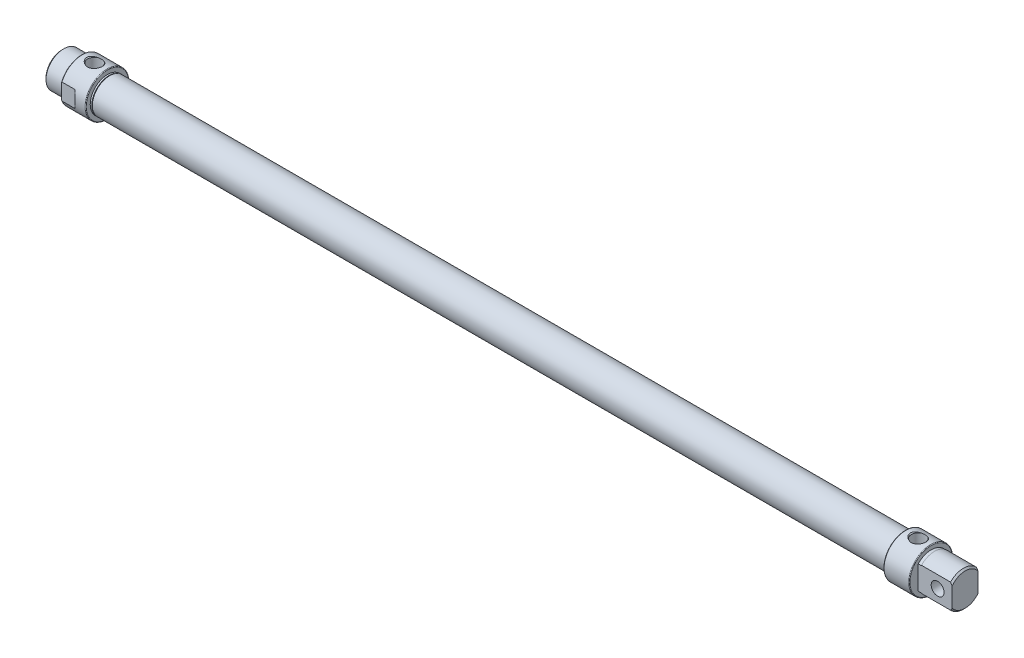
SolidWorks part; units mm, degrees
ref_plane "前视基准面" through (0, 0, 0) normal (0, 0, 1) x (1, 0, 0)
ref_plane "上视基准面" through (0, 0, 0) normal (0, 1, 0) x (1, 0, 0)
ref_plane "右视基准面" through (0, 0, 0) normal (1, 0, 0) x (0, 0, -1)
sketch "草图1" plane through (0, 0, 0) normal (0, 0, 1) x (1, 0, 0)
  line L0 (0, 0) -> (0, 10.08)
  line L1 (0, 10.08) -> (0.92, 11)
  line L2 (0.92, 11) -> (12, 11)
  line L3 (12, 11) -> (12, 13.1)
  line L4 (12.4, 13.5) -> (27.6, 13.5)
  line L5 (28, 13.1) -> (28, 10.7)
  line L6 (28, 10.7) -> (29, 10.7)
  line L7 (29, 10.7) -> (29, 10.2)
  line L8 (29, 10.2) -> (29.3, 10.7)
  line L9 (29.3, 10.7) -> (520.7, 10.7)
  line L10 (520.7, 10.7) -> (521, 10.2)
  line L11 (521, 10.2) -> (521, 10.7)
  line L12 (521, 10.7) -> (522, 10.7)
  line L13 (522, 10.7) -> (522, 13.1)
  line L14 (522.4, 13.5) -> (537.6, 13.5)
  line L15 (538, 13.1) -> (538, 0)
  line L16 (538, 0) -> (0, 0)
  line L17 (538, 0) -> (0, 0) construction
  arc A0 (12, 13.1) -> (12.4, 13.5) centre (12.4, 13.1) cw
  arc A1 (27.6, 13.5) -> (28, 13.1) centre (27.6, 13.1) cw
  arc A2 (522, 13.1) -> (522.4, 13.5) centre (522.4, 13.1) cw
  arc A3 (537.6, 13.5) -> (538, 13.1) centre (537.6, 13.1) cw
revolve "旋转1" add sketch "草图1" angle 360 about L17 reverse direction yes
cosmetic thread "装饰螺纹线1" parameters "D1"=10, "D2"=20.16
sketch "草图2" plane through (0, 0, 0) normal (0, 0, 1) x (1, 0, 0)
  line L0 (538, 0) -> (538, 10.85)
  line L1 (538, 10.85) -> (540, 10.85)
  line L2 (540, 10.85) -> (540, 11)
  line L3 (540, 11) -> (558, 11)
  line L4 (558, 11) -> (559, 10)
  line L5 (559, 10) -> (559, 0)
  line L6 (559, 0) -> (538, 0)
  line L7 (559, 0) -> (538, 0) construction
revolve "旋转2" add sketch "草图2" angle 360 about L7 reverse direction yes
cosmetic thread "装饰螺纹线2" parameters "D1"=19, "D2"=18.933
ref_plane "基准面4" through (12, 0, 0) normal (1, 0, 0) x (0, 0, -1)
ref_plane "基准面5" through (559, 0, 0) normal (1, 0, 0) x (0, 0, -1)
sketch "草图3" plane through (559, 0, 0) normal (1, 0, 0) x (0, 0, -1)
  line L0 (-18, 21) -> (-18, -21)
  line L1 (-18, -21) -> (18, -21)
  line L2 (18, -21) -> (18, 21)
  line L3 (18, 21) -> (-18, 21)
  line L4 (-8, 11) -> (-8, -11)
  line L5 (-8, -11) -> (8, -11)
  line L6 (8, -11) -> (8, 11)
  line L7 (8, 11) -> (-8, 11)
extrude "切除-拉伸1" cut sketch "草图3" against normal blind 21
ref_plane "基准面6" through (550, 0, 0) normal (1, 0, 0) x (0, 0, -1)
sketch "草图4" plane through (550, 0, 0) normal (1, 0, 0) x (0, 0, -1)
  line L0 (-8, 0) -> (-8, 4)
  line L1 (-8, 4) -> (8, 4)
  line L2 (8, 4) -> (8, 0)
  line L3 (8, 0) -> (-8, 0)
  line L4 (8, 0) -> (-8, 0) construction
revolve "切除-旋转1" cut sketch "草图4" angle 360 about L4 reverse direction yes
sketch "草图5" plane through (0, 0, 0) normal (0, 0, 1) x (1, 0, 0)
  line L0 (20, 13.5) -> (24.864, 13.5)
  line L1 (24.864, 13.5) -> (24.283, 12.919)
  line L2 (24.283, 12.919) -> (24.283, 5.5)
  line L3 (24.283, 5.5) -> (20, 5.5)
  line L4 (20, 5.5) -> (20, 13.5)
  line L5 (20, 5.5) -> (20, 13.5) construction
revolve "切除-旋转2" cut sketch "草图5" angle 360 about L5 reverse direction yes
cosmetic thread "装饰螺纹线3" parameters "D1"=7.419, "D2"=9.728
sketch "草图6" plane through (0, 0, 0) normal (0, 0, 1) x (1, 0, 0)
  line L0 (530, 13.5) -> (534.864, 13.5)
  line L1 (534.864, 13.5) -> (534.283, 12.919)
  line L2 (534.283, 12.919) -> (534.283, 5.5)
  line L3 (534.283, 5.5) -> (530, 5.5)
  line L4 (530, 5.5) -> (530, 13.5)
  line L5 (530, 5.5) -> (530, 13.5) construction
revolve "切除-旋转3" cut sketch "草图6" angle 360 about L5 reverse direction yes
cosmetic thread "装饰螺纹线4" parameters "D1"=7.419, "D2"=9.728
sketch "草图7" plane through (0, 0, 0) normal (0, 1, 0) x (1, 0, 0)
  line L0 (-4, -13.5) -> (21.5, -13.5)
  line L1 (21.5, -13.5) -> (20.5, -12.5)
  line L2 (20.5, -12.5) -> (-2, -12.5)
  line L3 (-2, -12.5) -> (-2, 12.5)
  line L4 (-2, 12.5) -> (20.5, 12.5)
  line L5 (20.5, 12.5) -> (21.5, 13.5)
  line L6 (21.5, 13.5) -> (-4, 13.5)
  line L7 (-4, 13.5) -> (-4, -13.5)
extrude "切除-拉伸2" cut sketch "草图7" along normal blind 27 and the other way blind 27
sketch "草图8" plane through (0, 0, 0) normal (0, 0, 1) x (1, 0, 0)
  line L0 (0, 0) -> (0, 4)
  line L1 (0, 4) -> (39, 4)
  line L2 (39, 4) -> (39, 10)
  line L3 (39, 10) -> (511, 10)
  line L4 (511, 10) -> (511, 0)
  line L5 (511, 0) -> (0, 0)
  line L6 (511, 0) -> (0, 0) construction
revolve "切除-旋转4" cut sketch "草图8" angle 360 about L6 reverse direction yes
ref_plane "基准面7" through (20, 0, 0) normal (1, 0, 0) x (0, 0, -1)
ref_plane "基准面8" through (0, 16.8, 0) normal (0, 1, 0) x (1, 0, 0)
ref_plane "基准面9" through (530, 0, 0) normal (1, 0, 0) x (0, 0, -1)
ref_plane "基准面10" through (4.5, 0, 0) normal (1, 0, 0) x (0, 0, -1)
ref_plane "基准面11" through (28, 0, 0) normal (1, 0, 0) x (0, 0, -1)
ref_plane "基准面12" through (12, 0, 0) normal (1, 0, 0) x (0, 0, -1)
ref_plane "基准面13" through (538, 0, 0) normal (1, 0, 0) x (0, 0, -1)
ref_plane "基准面14" through (545.5, 0, 0) normal (1, 0, 0) x (0, 0, -1)
ref_plane "基准面15" through (29, 0, 0) normal (1, 0, 0) x (0, 0, -1)
ref_plane "基准面16" through (521, 0, 0) normal (1, 0, 0) x (0, 0, -1)
ref_plane "IP_SWITCH1 XY" through (29, 0, 0) normal (-1, 0, 0) x (0, 0, 1)
ref_plane "IP_SWITCH1 XZ" through (0, 0, 0) normal (0, 1, 0) x (1, 0, 0)
ref_plane "IP_SWITCH1 YZ" through (0, 0, 0) normal (0, 0, -1) x (-1, 0, 0)
ref_axis "IP_SWITCH1 X" through (29, 0, 80.9) along (0, 0, -1)
ref_axis "IP_SWITCH1 Y" through (29, 50, 0) along (0, -1, 0)
ref_axis "IP_SWITCH1 Z" through (-80.9, 0, 0) along (1, 0, 0)
sketch3d "IP_SWITCH1"
  point P0 (29, 0, 0)
ref_plane "IP_SWITCH2 XY" through (521, 0, 0) normal (1, 0, 0) x (0, 0, -1)
ref_plane "IP_SWITCH2 XZ" through (0, 0, 0) normal (0, -1, 0) x (-1, 0, 0)
ref_plane "IP_SWITCH2 YZ" through (0, 0, 0) normal (0, 0, -1) x (-1, 0, 0)
ref_axis "IP_SWITCH2 X" through (521, 0, 80.9) along (0, 0, -1)
ref_axis "IP_SWITCH2 Y" through (521, -50, 0) along (0, 1, 0)
ref_axis "IP_SWITCH2 Z" through (80.9, 0, 0) along (-1, 0, 0)
sketch3d "IP_SWITCH2"
  point P0 (521, 0, 0)
ref_plane "body-dummy XY" through (28, 0, 0) normal (1, 0, 0) x (0, 0, -1)
ref_plane "body-dummy XZ" through (0, 0, 0) normal (0, -1, 0) x (-1, 0, 0)
ref_plane "body-dummy YZ" through (0, 0, 0) normal (0, 0, -1) x (-1, 0, 0)
ref_axis "body-dummy X" through (28, 0, 80.9) along (0, 0, -1)
ref_axis "body-dummy Y" through (28, -50, 0) along (0, 1, 0)
ref_axis "body-dummy Z" through (80.9, 0, 0) along (-1, 0, 0)
sketch3d "body-dummy"
  point P0 (28, 0, 0)
ref_plane "body-sdb XY" through (0, 0, 0) normal (0, 0, 1) x (1, 0, 0)
ref_plane "body-sdb XZ" through (0, 0, 0) normal (0, -1, 0) x (-1, 0, 0)
ref_plane "body-sdb YZ" through (550, 0, 0) normal (1, 0, 0) x (0, 0, -1)
ref_axis "body-sdb X" through (-80.9, 0, 0) along (1, 0, 0)
ref_axis "body-sdb Y" through (550, -50, 0) along (0, 1, 0)
ref_axis "body-sdb Z" through (550, 0, 80.9) along (0, 0, -1)
sketch3d "body-sdb"
  point P0 (550, 0, 0)
ref_plane "fa-body XY" through (12, 0, 0) normal (-1, 0, 0) x (0, 0, 1)
ref_plane "fa-body XZ" through (0, 0, 0) normal (0, 1, 0) x (1, 0, 0)
ref_plane "fa-body YZ" through (0, 0, 0) normal (0, 0, -1) x (-1, 0, 0)
ref_axis "fa-body X" through (12, 0, 80.9) along (0, 0, -1)
ref_axis "fa-body Y" through (12, 50, 0) along (0, -1, 0)
ref_axis "fa-body Z" through (-80.9, 0, 0) along (1, 0, 0)
sketch3d "fa-body"
  point P0 (12, 0, 0)
ref_plane "lb-body XY" through (538, 0, 0) normal (1, 0, 0) x (0, 0, -1)
ref_plane "lb-body XZ" through (0, 0, 0) normal (0, -1, 0) x (-1, 0, 0)
ref_plane "lb-body YZ" through (0, 0, 0) normal (0, 0, -1) x (-1, 0, 0)
ref_axis "lb-body X" through (538, 0, 80.9) along (0, 0, -1)
ref_axis "lb-body Y" through (538, -50, 0) along (0, 1, 0)
ref_axis "lb-body Z" through (80.9, 0, 0) along (-1, 0, 0)
sketch3d "lb-body"
  point P0 (538, 0, 0)
ref_plane "nut1-body XY" through (545.5, 0, 0) normal (1, 0, 0) x (0, 0, -1)
ref_plane "nut1-body XZ" through (0, 0, 0) normal (0, -1, 0) x (-1, 0, 0)
ref_plane "nut1-body YZ" through (0, 0, 0) normal (0, 0, -1) x (-1, 0, 0)
ref_axis "nut1-body X" through (545.5, 0, 80.9) along (0, 0, -1)
ref_axis "nut1-body Y" through (545.5, -50, 0) along (0, 1, 0)
ref_axis "nut1-body Z" through (80.9, 0, 0) along (-1, 0, 0)
sketch3d "nut1-body"
  point P0 (545.5, 0, 0)
ref_plane "nut2-body XY" through (4.5, 0, 0) normal (-1, 0, 0) x (0, 0, 1)
ref_plane "nut2-body XZ" through (0, 0, 0) normal (0, 1, 0) x (1, 0, 0)
ref_plane "nut2-body YZ" through (0, 0, 0) normal (0, 0, -1) x (-1, 0, 0)
ref_axis "nut2-body X" through (4.5, 0, 80.9) along (0, 0, -1)
ref_axis "nut2-body Y" through (4.5, 50, 0) along (0, -1, 0)
ref_axis "nut2-body Z" through (-80.9, 0, 0) along (1, 0, 0)
sketch3d "nut2-body"
  point P0 (4.5, 0, 0)
ref_plane "rod-body XY" through (0, 0, 0) normal (-1, 0, 0) x (0, 0, 1)
ref_plane "rod-body XZ" through (0, 0, 0) normal (0, 1, 0) x (1, 0, 0)
ref_plane "rod-body YZ" through (0, 0, 0) normal (0, 0, -1) x (-1, 0, 0)
ref_axis "rod-body X" through (0, 0, 80.9) along (0, 0, -1)
ref_axis "rod-body Y" through (0, 50, 0) along (0, -1, 0)
ref_axis "rod-body Z" through (-80.9, 0, 0) along (1, 0, 0)
sketch3d "rod-body"
  point P0 (0, 0, 0)
ref_plane "rod-nut XY" through (0, 0, 0) normal (-1, 0, 0) x (0, 0, 1)
ref_plane "rod-nut XZ" through (0, 0, 0) normal (0, 1, 0) x (1, 0, 0)
ref_plane "rod-nut YZ" through (0, 0, 0) normal (0, 0, -1) x (-1, 0, 0)
ref_axis "rod-nut X" through (0, 0, 80.9) along (0, 0, -1)
ref_axis "rod-nut Y" through (0, 50, 0) along (0, -1, 0)
ref_axis "rod-nut Z" through (-80.9, 0, 0) along (1, 0, 0)
sketch3d "rod-nut"
  point P0 (0, 0, 0)
